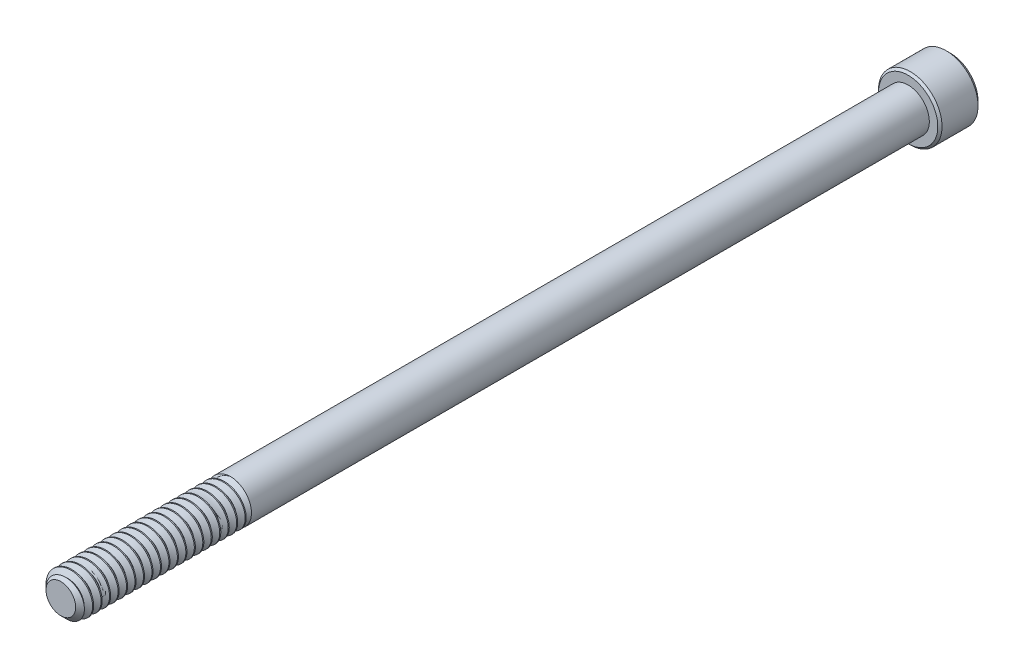
SolidWorks part; units mm, degrees
material "Cast Alloy Steel"
ref_plane "Front Plane" through (0, 0, 0) normal (0, 0, 1) x (1, 0, 0)
ref_plane "Top Plane" through (0, 0, 0) normal (0, 1, 0) x (1, 0, 0)
ref_plane "Right Plane" through (0, 0, 0) normal (1, 0, 0) x (0, 0, -1)
sketch "Sketch1" plane through (0, 0, 0) normal (0, 0, 1) x (1, 0, 0)
  line L0 (0, 3.175) -> (0, -3.175) construction
  circle A0 centre (0, 0) radius 3.175
  dimension "OD" = 6.35
extrude "Extrude1" add sketch "Sketch1" against normal blind 127
sketch "Sketch2" plane through (0, 0, 0) normal (0, 0, 1) x (1, 0, 0)
  circle A0 centre (0, 0) radius 3.175 construction
  circle A1 centre (0, 0) radius 3.175
curve "Helix/Spiral1" pitch 1.27 height 27.94 turns 22 parameters "pitch"=1.27
chamfer "Chamfer3" distance 0.9525 angle 45 1 edges at (3.175, 0, 0)
sketch "Sketch3" plane through (0, 0, 0) normal (1, 0, 0) x (0, 0, -1)
  line L0 (-1.1112, 3.175) -> (-0.635, 2.3501)
  line L1 (-0.635, 2.3501) -> (-0.4763, 2.3501)
  line L2 (-0.4763, 2.3501) -> (0, 3.175)
  line L3 (-1.1112, 3.175) -> (0, 3.175)
  line L4 (-0.5556, 3.175) -> (-0.5556, 2.3501) construction
  line L5 (-0.8731, 2.7626) -> (-0.2381, 2.7626) construction
  line L6 (0, 3.175) -> (0, -3.175) construction
  dimension "D1" = 0.1588
  dimension "D2" = 0.635
  dimension "D3" = 60
sweep "Cut-Sweep1" cut profiles "Sketch3" path "Helix/Spiral1"
sketch "Sketch5" plane through (0, 0, 0) normal (1, 0, 0) x (0, 0, -1)
  line L1 (127, 3.175) -> (25.4, 3.175)
  line L2 (127, 3.175) -> (127, 0)
  line L3 (127, 0) -> (25.4, 0)
  line L4 (25.4, 3.175) -> (25.4, 0) construction
  line L6 (0, 0) -> (9.9695, 0) construction
  line L8 (25.4, 3.175) -> (22.225, 0)
  line L9 (22.225, 0) -> (25.4, 0)
  line L10 (127, -3.175) -> (127, 3.175) construction
  dimension "D1" = 45
  dimension "Thread min" = 25.4
revolve "partially thread" add sketch "Sketch5" angle 360 about L6
sketch "Sketch6" plane through (0, 0, -127) normal (0, 0, -1) x (-1, 0, 0)
  circle A0 centre (0, 0) radius 4.7625
  dimension "head dia" = 9.525
extrude "Extrude2" add sketch "Sketch6" along normal blind 6.35
sketch "Sketch7" plane through (0, 0, -133.35) normal (0, 0, -1) x (-1, 0, 0)
  line L1 (0, 2.7496) -> (-2.3812, 1.3748)
  line L2 (-2.3812, 1.3748) -> (-2.3813, -1.3748)
  line L3 (-2.3813, -1.3748) -> (0, -2.7496)
  line L4 (0, -2.7496) -> (2.3813, -1.3748)
  line L5 (2.3813, -1.3748) -> (2.3813, 1.3748)
  line L6 (2.3813, 1.3748) -> (0, 2.7496)
  circle A0 centre (0, 0) radius 2.3813 construction
  dimension "hex dia" = 4.7625
extrude "Cut-Extrude1" cut sketch "Sketch7" against normal blind 3.5719
sketch "Sketch8" plane through (0, 0, -133.35) normal (0, 0, -1) x (-1, 0, 0)
  circle A0 centre (0, 0) radius 2.7496
extrude "Cut-Extrude2" cut sketch "Sketch8" against normal blind 0.635 draft 45
chamfer "Chamfer1" distance 0.635 angle 45 1 edges at (-4.7625, 0, -133.35)
chamfer "Chamfer2" distance 0.3175 angle 45 1 edges at (-4.7625, 0, -127)
sketch "Sketch9" plane through (0, 0, 0) normal (1, 0, 0) x (0, 0, -1)
  line L0 (0, 3.175) -> (0, -3.175) construction
  line L1 (6.985, 3.175) -> (6.985, -3.175) construction
  line L2 (127, 4.7625) -> (127, -4.7625) construction
  line L3 (133.35, 4.7625) -> (133.35, -4.7625) construction
  line L4 (133.35, 0) -> (0, 0) construction
  line L5 (61.6852, 3.175) -> (61.6852, -3.175) construction
  dimension "D1" = 6.985
  dimension "D2" = 6.35
  dimension "D3" = 9.525
  dimension "D4" = 127
  dimension "Thread Length" = 61.6852
equation "\"D3@Helix/Spiral1\" = \"Thread min@Sketch5\"+(\"pitch@Helix/Spiral1\"*2)"
equation "\"D1@Sketch3\" = \"pitch@Helix/Spiral1\"*.125"
equation "\"D2@Sketch3\" = \"pitch@Helix/Spiral1\"*.5"
equation "\"D1@Cut-Extrude1\" = \"hex dia@Sketch7\"*.75"
equation "\"D1@Chamfer1\" = \"head depth@Extrude2\"/10"
equation "\"D1@Sketch9\" = \"pitch@Helix/Spiral1\"*5.5"
equation "\"D1@Chamfer2\" = \"D1@Chamfer1\"/2"
equation "\"D1@Cut-Extrude2\" = \"D1@Chamfer2\"*2"
equation "\"D1@Chamfer3\" = \"pitch@Helix/Spiral1\"*.750"
equation "\"D2@Sketch9\" = \"head depth@Extrude2\""
equation "\"D3@Sketch9\" = \"head dia@Sketch6\""
equation "\"D4@Sketch9\" = \"screw length@Extrude1\""
